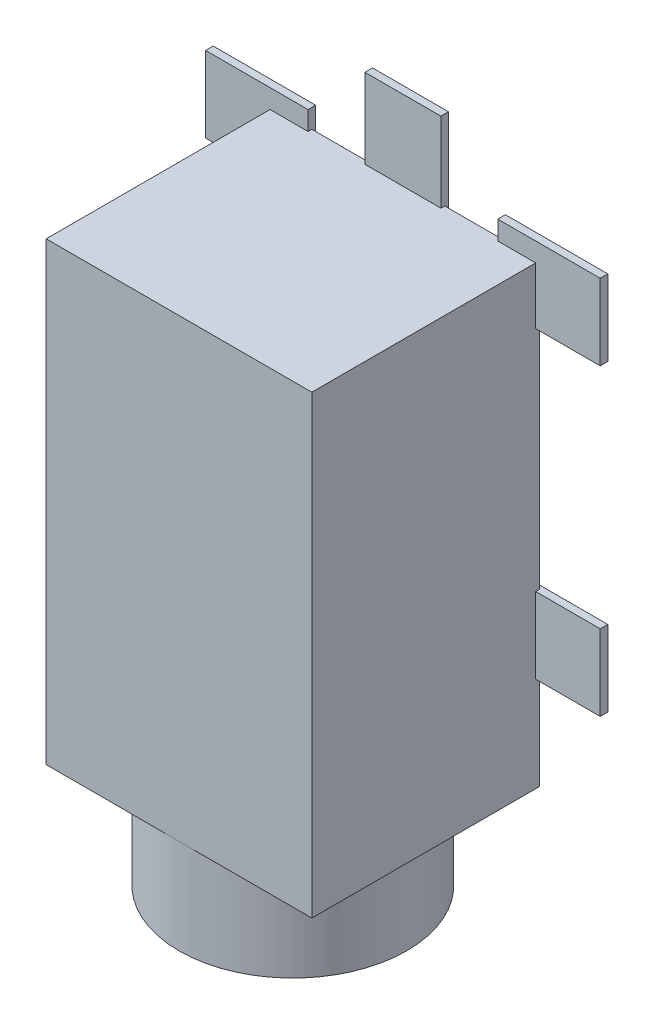
SolidWorks part; units mm, degrees
ref_plane "Front Plane" through (0, 0, 0) normal (0, 0, 1) x (1, 0, 0)
ref_plane "Top Plane" through (0, 0, 0) normal (0, 1, 0) x (1, 0, 0)
ref_plane "Right Plane" through (0, 0, 0) normal (1, 0, 0) x (0, 0, -1)
sketch "Sketch1" plane through (0, 0, 0) normal (0, 0, 1) x (1, 0, 0)
  line L1 (-3.5, 6) -> (3.5, 6)
  line L2 (-3.5, 6) -> (-3.5, -6)
  line L3 (-3.5, -6) -> (3.5, -6)
  line L4 (3.5, 6) -> (3.5, -6)
  line L5 (-3.5, 6) -> (3.5, -6) construction
  line L6 (-3.5, -6) -> (3.5, 6) construction
  point P0 (0, 0)
  dimension "D1" = 7
  dimension "D2" = 12
extrude "Boss-Extrude1" add sketch "Sketch1" along normal blind 6
sketch "Sketch2" plane through (0, -6, 0) normal (0, -1, 0) x (1, 0, 0)
  line L0 (0, 0) -> (0, 6) construction
  line L1 (-3.5, 6) -> (3.5, 6) construction
  circle A0 centre (0, 3) radius 3
  circle A1 centre (0, 3) radius 1.9
  dimension "D1" = 6
  dimension "D2" = 1.1
extrude "Boss-Extrude2" add sketch "Sketch2" along normal blind 2.5
sketch "Sketch3" plane through (0, 0, 0) normal (0, 0, -1) x (-1, 0, 0)
  line L0 (0, -6) -> (0, 6) construction
  line L1 (-3.5, 6) -> (3.5, 6) construction
  line L2 (0, -6) -> (-3.5, -6) construction
  circle A0 centre (0, -4) radius 0.5
  circle A1 centre (0, 3) radius 0.5
  dimension "D1" = 1
  dimension "D2" = 2
  dimension "D3" = 7
extrude "Boss-Extrude3" add sketch "Sketch3" along normal blind 1
sketch "Sketch4" plane through (0, 0, 0) normal (0, 0, -1) x (-1, 0, 0)
  line L0 (0, 0) -> (0, 5) construction
  line L1 (2.5, 6.5) -> (5.2, 6.5)
  line L2 (2.5, 6.5) -> (2.5, 4.5)
  line L3 (2.5, 4.5) -> (5.2, 4.5)
  line L4 (5.2, 6.5) -> (5.2, 4.5)
  line L5 (2.5, -1.5) -> (5.2, -1.5)
  line L6 (2.5, -1.5) -> (2.5, -3.5)
  line L7 (2.5, -3.5) -> (5.2, -3.5)
  line L8 (5.2, -1.5) -> (5.2, -3.5)
  line L17 (-1, 8.1) -> (1, 8.1)
  line L18 (-1, 8.1) -> (-1, 5)
  line L19 (-1, 5) -> (1, 5)
  line L20 (1, 8.1) -> (1, 5)
  line L21 (3.5, -6) -> (0, -6) construction
  line L22 (3.5, 6) -> (3.5, -6) construction
  line L23 (-3.5, 6) -> (3.5, 6) construction
  line L24 (-5.2, -1.5) -> (-5.2, -3.5)
  line L25 (-2.5, -3.5) -> (-5.2, -3.5)
  line L26 (-2.5, -1.5) -> (-2.5, -3.5)
  line L27 (-2.5, -1.5) -> (-5.2, -1.5)
  line L28 (-5.2, 6.5) -> (-5.2, 4.5)
  line L29 (-2.5, 4.5) -> (-5.2, 4.5)
  line L30 (-2.5, 6.5) -> (-2.5, 4.5)
  line L31 (-2.5, 6.5) -> (-5.2, 6.5)
  point P10 (5.2, -2.5)
  point P14 (5.2, 5.5)
  dimension "D1" = 3.5
  dimension "D2" = 2
  dimension "D3" = 5.2
  dimension "D4" = 1
  dimension "D5" = 11.5
  dimension "D6" = 2.1
  dimension "D7" = 1
extrude "Boss-Extrude4" add sketch "Sketch4" along normal mid plane 0.2
ref_axis "Axis1" through (0, -8.5, 3) along (0, 1, 0)
